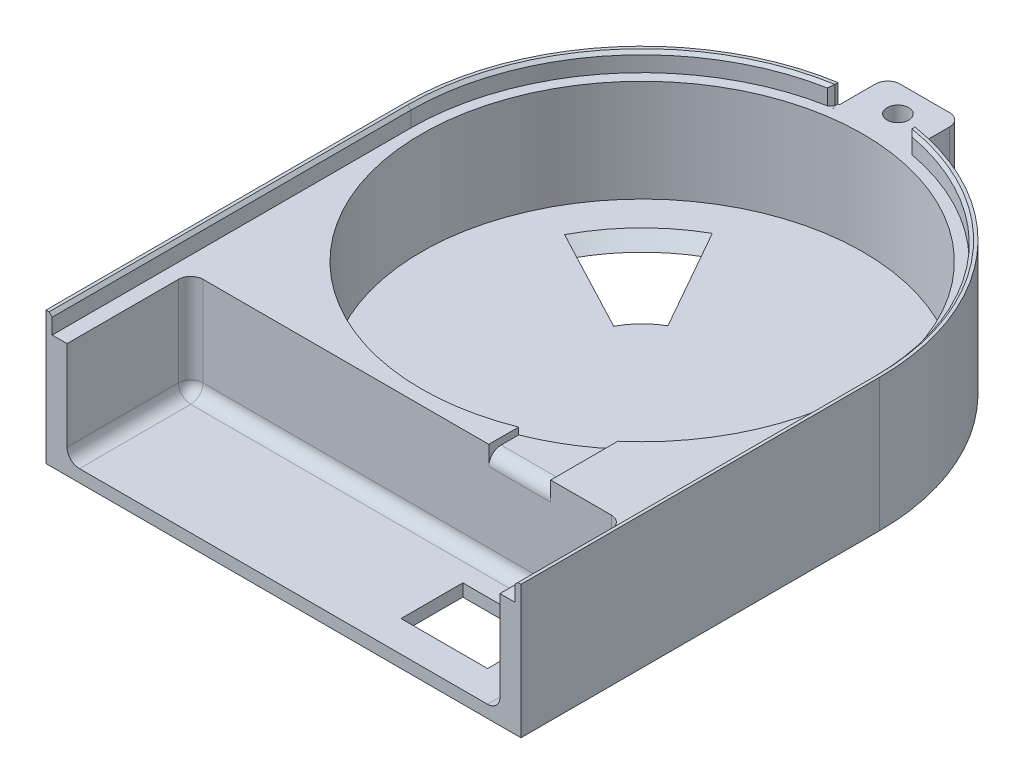
SolidWorks part; units mm, degrees
ref_plane "Front Plane" through (0, 0, 0) normal (0, 0, 1) x (1, 0, 0)
ref_plane "Top Plane" through (0, 0, 0) normal (0, 1, 0) x (1, 0, 0)
ref_plane "Right Plane" through (0, 0, 0) normal (1, 0, 0) x (0, 0, -1)
sketch "Sketch2" plane through (0, 0, 0) normal (0, 1, 0) x (1, 0, 0)
  arc B0 (-13.7477, 4.25) -> (13.7477, 4.25) centre (0, 8) ccw
  line B1 (-14.2816, -38) -> (35, -38)
  arc B2 (37, 0) -> (-37, 0) centre (0, 0) ccw
  arc B3 (-9, 19.0482) -> (-13.7477, 11.75) centre (0, 8) ccw
  arc B4 (-9, 30.6041) -> (-22.2816, -22.8285) centre (0, 0) ccw
  line B5 (-35, -68) -> (-35, -38)
  line B6 (-35, -68) -> (-37, -68)
  line B7 (35, -68) -> (35, -38)
  line B8 (37, -68) -> (37, 0)
  arc B9 (-9, -30.7083) -> (9, -30.7083) centre (0, 0) ccw
  line B10 (9, -30.7083) -> (2.6683, -14.7608)
  line B11 (37, -68) -> (35, -68)
  arc B12 (-9, 23.859) -> (-14.2816, -21.1255) centre (0, 0) ccw
  line B13 (-35, -38) -> (-22.2816, -38)
  line B14 (-22.2816, -22.8285) -> (-22.2816, -38)
  line B15 (-14.2816, -38) -> (-14.2816, -21.1255)
  line B16 (-37, 0) -> (-37, -68)
  arc B17 (-2.6683, -14.7608) -> (2.6683, -14.7608) centre (0, 0) ccw
  line B18 (9, 19.0482) -> (9, 33.8231)
  line B19 (-2.6683, -14.7608) -> (-9, -30.7083)
  arc B20 (-17.5, 11.75) -> (-17.5, 4.25) centre (-17.5, 8) ccw
  line B21 (-17.5, 11.75) -> (-13.7477, 11.75)
  arc B22 (17.5, 4.25) -> (17.5, 11.75) centre (17.5, 8) ccw
  arc B23 (13.7477, 11.75) -> (9, 19.0482) centre (0, 8) ccw
sketch_block_instance "bottom1-1"
sketch_block "Block1"
sketch "Sketch3" plane through (0, 0, 0) normal (0, 1, 0) x (1, 0, 0)
  line L0 (-37, 0) -> (-37, -58)
  line L1 (-37, -58) -> (-35, -58)
  line L2 (-35, -58) -> (-35, -38)
  line L3 (-35, -38) -> (35, -38)
  line L4 (35, -38) -> (35, -58)
  line L5 (35, -58) -> (37, -58)
  line L6 (37, -58) -> (37, 0)
  arc A0 (37, 0) -> (-37, 0) centre (0, 0) ccw
  circle A1 centre (0, 0) radius 35.7
  dimension "D1" = 71.4
  dimension "D2" = 20
  dimension "D3" = 20
sketch "Sketch4" plane through (0, 0, 0) normal (0, 1, 0) x (1, 0, 0)
  line L0 (37, 0) -> (37, -58)
  line L1 (37, -58) -> (-37, -58)
  line L2 (-37, -58) -> (-37, 0)
  line L3 (0, 0) -> (-11.5, 6.0622) construction
  line L4 (-6.4, 11.3155) -> (0, 0) construction
  line L6 (-11.5, 6.0622) -> (-24.7692, 13.057)
  line L7 (-6.4, 11.3155) -> (-13.7846, 24.3718)
  arc A0 (37, 0) -> (-37, 0) centre (0, 0) ccw
  arc A1 (-11.5, 6.0622) -> (-6.4, 11.3155) centre (0, 0) cw
  arc A2 (-24.7692, 13.057) -> (-13.7846, 24.3718) centre (0, 0) cw
  dimension "D1" = 20
  dimension "D2" = 15
  dimension "D4" = 6.4
  dimension "D3" = 13
  dimension "D5" = 11.5
extrude "Boss-Extrude1" add sketch "Sketch4" along normal blind 2
extrude "Boss-Extrude2" add sketch "Sketch3" along normal blind 18.5
sketch "Sketch5" plane through (0, 0, 0) normal (0, 1, 0) x (1, 0, 0)
  line L0 (0, 0) -> (0, 52.155) construction
  line L1 (6, 35.7) -> (-6, 35.7)
  line L2 (-6, 35.7) -> (-6, 45.7)
  line L3 (-6, 45.7) -> (6, 45.7)
  line L4 (6, 35.7) -> (6, 45.7)
  line L5 (0, 45.7) -> (0, 37) construction
  line L6 (0, 45.7) -> (0, 35.7) construction
  line L7 (0, 45.7) -> (0, 37) construction
  line L8 (0, 37) -> (0, 41.35) construction
  circle A0 centre (0, 0) radius 35.7 construction
  circle A1 centre (0, 41.35) radius 1.75
  arc A2 (37, 0) -> (-37, 0) centre (0, 0) ccw construction
  point P10 (0, 45.7)
  point P11 (0, 35.7)
  dimension "D3" = 3.5
  dimension "D1" = 12
  dimension "D2" = 10
extrude "Boss-Extrude3" add sketch "Sketch5" along normal up to surface (18.5 mm away) up to face at (0, 18.5, 33.875)
sketch "Sketch6" plane through (0, 0, 0) normal (0, 1, 0) x (-1, 0, 0)
  line L15 (37.4, 0) -> (37.4, 58)
  line L16 (37.4, 0) -> (37.4, 58)
  line L17 (-6.0649, -36.905) -> (6.0649, -36.905)
  line L18 (-37.4, 58) -> (-37.4, 0)
  line L19 (-37.4, 58) -> (-37.4, 0)
  line L20 (37.4, 58) -> (35, 58)
  line L21 (35, 58) -> (35, 38)
  line L22 (35, 38) -> (-35, 38)
  line L23 (-35, 38) -> (-35, 58)
  line L24 (-35, 58) -> (-37.4, 58)
  line L25 (37.4, 0) -> (36.4, 0) construction
  arc A15 (6.0649, -36.905) -> (37.4, 0) centre (0, 0) ccw
  arc A16 (6.0649, -36.905) -> (37.4, 0) centre (0, 0) ccw
  circle A17 centre (0, 0) radius 36.4
  arc A18 (-37.4, 0) -> (-6.0649, -36.905) centre (0, 0) ccw
  arc A19 (-37.4, 0) -> (-6.0649, -36.905) centre (0, 0) ccw
  dimension "D1" = 0.4
  dimension "D3" = 1
  dimension "D2" = 0.4
extrude "Boss-Extrude5" add sketch "Sketch6" along normal up to surface (18.5 mm away) up to face at (0, 18.5, 35.7)
sketch "Sketch7" plane through (0, 0, 0) normal (0, 1, 0) x (1, 0, 0)
  line L0 (37.4, 0) -> (37.4, -58)
  line L1 (38.4, -58) -> (37.4, -58)
  line L2 (-37.4, 0) -> (-37.4, -58)
  line L3 (-37.4, -58) -> (-38.4, -58)
  line L9 (-38.4, 0) -> (-38.4, -58)
  line L10 (-38.4, 0) -> (-38.4, -58)
  line L11 (-6.227, 37.8917) -> (6.227, 37.8917)
  line L12 (38.4, -58) -> (38.4, 0)
  line L13 (38.4, -58) -> (38.4, 0)
  line L20 (-38.4, 0) -> (-37.4, 0) construction
  arc A8 (-6.227, 37.8917) -> (-38.4, 0) centre (0, 0) ccw
  arc A9 (-6.227, 37.8917) -> (-38.4, 0) centre (0, 0) ccw
  arc A12 (38.4, 0) -> (6.227, 37.8917) centre (0, 0) ccw
  arc A13 (38.4, 0) -> (6.227, 37.8917) centre (0, 0) ccw
  arc A14 (37.4, 0) -> (-37.4, 0) centre (0, 0) ccw
  dimension "D1" = 1
  dimension "D2" = 1
extrude "Boss-Extrude6" add sketch "Sketch7" along normal offset from surface (21.5 mm away) 3 up to face at (0, 18.5, 4.1051) offset beyond the face yes
sketch "Sketch8" plane through (0, 0, -45.7) normal (0, 0, -1) x (-1, 0, 0)
  line L0 (0, 18.5) -> (-6.227, 18.5) construction
  line L1 (-6, 18.5) -> (6, 18.5) construction
  line L2 (-6.227, 21.5) -> (-6.227, 0) construction
  line L4 (-6.227, 18.5) -> (6.227, 18.5)
  line L5 (-6.227, 18.5) -> (-6.227, 23.5)
  line L6 (-6.227, 23.5) -> (6.227, 23.5)
  line L7 (6.227, 18.5) -> (6.227, 23.5)
  dimension "D1" = 5
extrude "Cut-Extrude1" cut sketch "Sketch8" against normal blind 12
sketch "Sketch9" plane through (0, 0, 38) normal (0, 0, 1) x (1, 0, 0)
  line L0 (35, 18.5) -> (35, 2) construction
  line L1 (13.2, 20.4) -> (23.2, 20.4)
  line L2 (13.2, 20.4) -> (13.2, 17.4)
  line L3 (13.2, 17.4) -> (23.2, 17.4)
  line L4 (23.2, 20.4) -> (23.2, 17.4)
  line L5 (-35, 2) -> (35, 2) construction
  dimension "D1" = 3
  dimension "D2" = 10
  dimension "D3" = 11.8
  dimension "D4" = 15.4
extrude "Cut-Extrude2" cut sketch "Sketch9" against normal blind 21
chamfer "Chamfer1" distance 0.5 angle 45 6 edges at (-6.227, 20, -36.878) (6.227, 20, -36.878) (28.5627, 21.5, -24.144) (37.4, 21.5, 29) (-28.5627, 21.5, -24.144) (-37.4, 21.5, 29)
fillet "Fillet1" radius 2 11 edges at (18.2, 17.4, 38) (-6, 9.25, -45.7) (6, 9.25, -45.7) (6, 0, -41.7959) (0, 0, -45.7) (-6, 0, -41.7959) (35, 2, 48) (0, 2, 38) (-35, 2, 48) (-35, 10.25, 38) (35, 10.25, 38)
chamfer "Chamfer2" distance 2 angle 45 2 edges at (-20.0899, 2, -19.5037) (-9.3275, 2, -9.0553)
sketch "Sketch10" plane through (0, 0, 0) normal (0, 1, 0) x (1, 0, 0)
  line L1 (28, -43) -> (14, -43)
  line L2 (28, -43) -> (28, -53)
  line L3 (28, -53) -> (14, -53)
  line L4 (14, -43) -> (14, -53)
  dimension "D1" = 10
  dimension "D2" = 14
  dimension "D3" = 43
  dimension "D4" = 14
extrude "Cut-Extrude3" cut sketch "Sketch10" along normal blind 13
